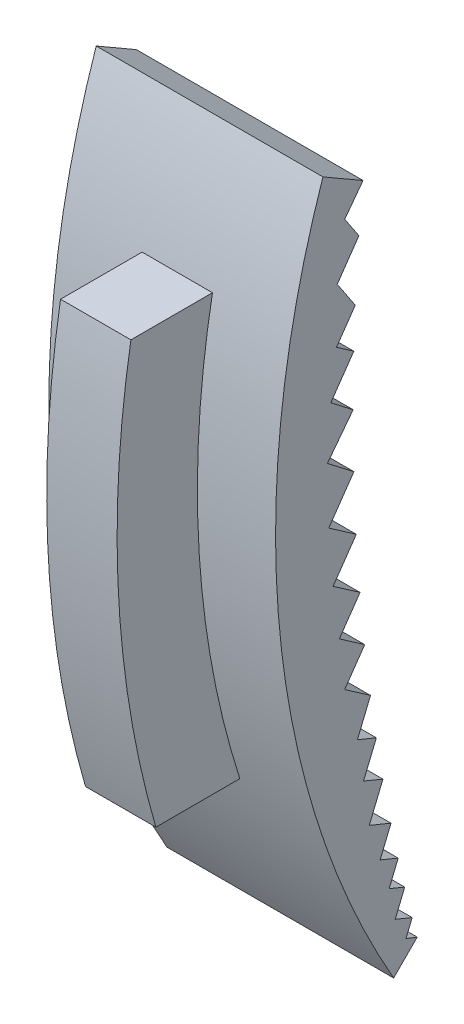
SolidWorks part; units mm, degrees
material "ABS"
ref_plane "Front Plane" through (0, 0, 0) normal (0, 0, 1) x (1, 0, 0)
ref_plane "Top Plane" through (0, 0, 0) normal (0, 1, 0) x (1, 0, 0)
ref_plane "Right Plane" through (0, 0, 0) normal (1, 0, 0) x (0, 0, -1)
sketch "Sketch1" plane through (0, 0, 0) normal (1, 0, 0) x (0, 0, -1)
  line L0 (13.97, 5.7716) -> (12.7, 4.5016)
  line L1 (12.7, 4.5016) -> (13.97, 4.5016) construction
  line L2 (13.97, 4.5016) -> (13.97, 5.7716) construction
  line L3 (0, 0) -> (12.7, 0) construction
  line L4 (12.7, 0) -> (12.7, 4.5016) construction
  line L5 (7.161, 37.084) -> (2.7748, 37.084)
  line L6 (8.6325, 13.716) -> (4.1172, 13.716)
  arc A0 (8.9448, 43.8527) -> (12.7, 4.5016) centre (54.1734, 28.3141) ccw
  arc A1 (12.4317, 51.6531) -> (8.9448, 43.8527) centre (54.1734, 28.3141) ccw
  arc A2 (12.4317, 51.6531) -> (13.97, 5.7716) centre (112.1185, 32.0287) ccw
  arc A3 (2.7748, 37.084) -> (4.1172, 13.716) centre (54.1734, 28.3141) ccw
  dimension "D3" = 101.6
  dimension "D1" = 1.27
  dimension "D2" = 45
  dimension "D4" = 37.084
  dimension "D5" = 13.716
extrude "Yükseklik-Ekstrüzyon1" add sketch "Sketch1" along normal mid plane 3.7846 contours A2 A1 A0 L0 | L5 A3 L6 A0 region at (0, 26.2135, -9.5328) region at (0, 25.3444, -4.7454)
extrude "Yükseklik-Ekstrüzyon2" add sketch "Sketch1<3>" along normal mid plane 12.192 contours A2 A1 A0 L0 region at (0, 26.2135, -9.5328)
sketch "Sketch1<3>" plane through (0, 0, 0) normal (1, 0, 0) x (0, 0, -1) same geometry as "Sketch1"
sketch "Çizim1" plane through (6.096, 0, 0) normal (1, 0, 0) x (0, 0, -1)
  line L0 (7.62, 44.45) -> (15.24, 40.0506)
  line L1 (7.62, 44.45) -> (7.62, 52.7506)
  line L2 (7.62, 52.7506) -> (15.24, 52.7506)
  line L3 (15.24, 52.7506) -> (15.24, 40.0506)
  line L4 (7.62, 44.45) -> (0, 44.45) construction
  line L5 (0, 44.45) -> (0, 0) construction
  dimension "D1" = 120
  dimension "D2" = 7.62
  dimension "D3" = 44.45
  dimension "D4" = 12.7
  dimension "D5" = 7.62
extrude "Kes-Ekstrüzyon1" cut sketch "Çizim1" against normal blind 12.192 contours L1 L2 L3 L0
sketch "Çizim2" plane through (6.096, 0, 0) normal (1, 0, 0) x (0, 0, -1)
  line L0 (11.056, 42.4662) -> (10.0705, 41.1538)
  line L1 (10.0705, 41.1538) -> (10.8337, 40.0073)
  line L2 (10.8337, 40.0073) -> (9.6663, 38.3268)
  line L3 (9.6663, 38.3268) -> (10.6369, 36.8689)
  line L4 (10.6369, 36.8689) -> (9.6257, 35.4132)
  line L5 (9.6257, 35.4132) -> (10.5593, 34.7647)
  line L6 (10.5593, 34.7647) -> (9.3198, 32.9804)
  line L7 (9.3198, 32.9804) -> (10.5233, 32.0575)
  line L8 (10.5233, 32.0575) -> (9.1355, 30.2477)
  line L9 (9.1355, 30.2477) -> (10.5647, 29.1518)
  line L10 (10.5647, 29.1518) -> (9.2104, 27.2021)
  line L11 (9.2104, 27.2021) -> (10.6933, 26.1719)
  line L12 (10.6933, 26.1719) -> (9.443, 24.372)
  line L13 (9.443, 24.372) -> (10.8947, 23.3635)
  line L14 (10.8947, 23.3635) -> (9.7786, 21.7569)
  line L15 (9.7786, 21.7569) -> (11.1459, 20.8071)
  line L16 (11.1459, 20.8071) -> (10.066, 19.2525)
  line L17 (10.066, 19.2525) -> (11.4577, 18.2857)
  line L18 (11.4577, 18.2857) -> (10.7522, 16.5738)
  line L19 (10.7522, 16.5738) -> (11.7713, 16.1539)
  line L20 (11.7713, 16.1539) -> (11.0827, 14.4829)
  line L21 (11.0827, 14.4829) -> (12.1256, 14.0531)
  line L22 (12.1256, 14.0531) -> (11.3891, 12.266)
  line L23 (11.3891, 12.266) -> (12.5593, 11.7837)
  line L24 (12.5593, 11.7837) -> (11.9743, 10.3642)
  line L25 (11.9743, 10.3642) -> (12.9459, 9.9638)
  line L26 (12.9459, 9.9638) -> (12.4593, 8.783)
  line L27 (12.4593, 8.783) -> (13.297, 8.4378)
  line L28 (13.297, 8.4378) -> (12.7844, 7.1941)
  line L29 (12.7844, 7.1941) -> (13.6967, 6.8182)
  line L30 (13.6967, 6.8182) -> (13.3622, 6.0065)
  line L31 (13.3622, 6.0065) -> (13.97, 5.7716)
  line L32 (11.056, 42.4662) -> (16.6412, 42.4662)
  line L33 (16.6412, 42.4662) -> (16.6412, 5.7716)
  line L34 (16.6412, 5.7716) -> (13.97, 5.7716)
  line L35 (13.97, 5.7716) -> (12.7, 4.5016) construction
  arc A1 (11.056, 42.4662) -> (13.97, 5.7716) centre (112.4807, 32.0575) ccw construction
  arc A2 (11.056, 42.4662) -> (13.97, 5.7716) centre (112.1185, 32.0287) ccw construction
extrude "Kes-Ekstrüzyon2" cut sketch "Çizim2" against normal blind 12.192
